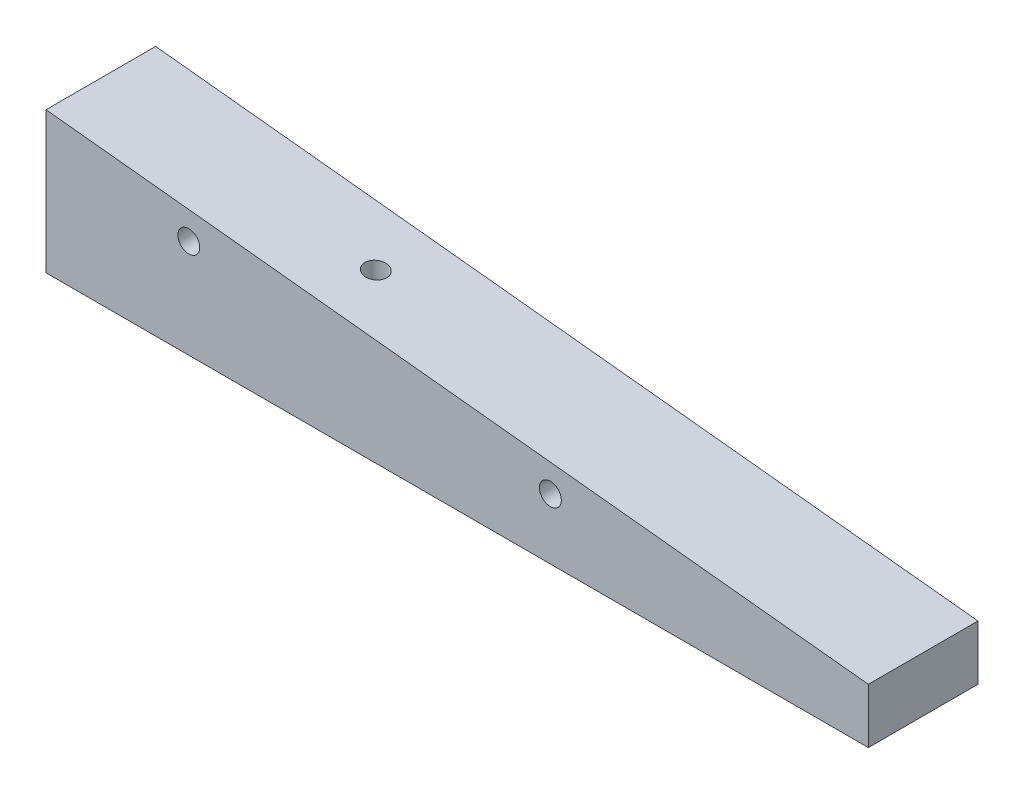
SolidWorks part; units mm, degrees
ref_plane "Front Plane" through (0, 0, 0) normal (0, 0, 1) x (1, 0, 0)
ref_plane "Top Plane" through (0, 0, 0) normal (0, 1, 0) x (1, 0, 0)
ref_plane "Right Plane" through (0, 0, 0) normal (1, 0, 0) x (0, 0, -1)
sketch "Sketch1" plane through (0, 0, 0) normal (0, 0, 1) x (1, 0, 0)
  line L2 (99.8523, 10) -> (-50.1477, 25.7656)
  line L4 (99.8523, 10) -> (99.8523, 0)
  line L5 (99.8523, 0) -> (-50.1477, 0)
  line L6 (-50.1477, 0) -> (-50.1477, 25.7656)
  line L7 (55, 0) -> (-55, 0) construction
  dimension "D1" = 150
  dimension "D2" = 6
  dimension "D3" = 10
extrude "Boss-Extrude1" add sketch "Sketch1" along normal mid plane 20
sketch "Sketch2" plane through (0, 0, 0) normal (0, -1, 0) x (1, 0, 0)
  circle A0 centre (0, 0) radius 2
  dimension "D1" = 4
extrude "Cut-Extrude1" cut sketch "Sketch2" against normal through all both and the other way through all
sketch "Sketch3" plane through (0, 0, -10) normal (0, 0, -1) x (-1, 0, 0)
  line L0 (-42.3716, 16.0415) -> (-41.849, 11.0689) construction
  line L1 (-99.8523, 10) -> (50.1477, 25.7656) construction
  line L2 (23.5813, 22.9734) -> (24.1039, 18.0008) construction
  circle A0 centre (24.1039, 18.0008) radius 2
  circle A1 centre (-41.849, 11.0689) radius 2
  dimension "D5" = 4
  dimension "D6" = 4
  dimension "D1" = 90
  dimension "D2" = 90
  dimension "D3" = 5
  dimension "D4" = 5
extrude "Cut-Extrude2" cut sketch "Sketch3" against normal through all both
